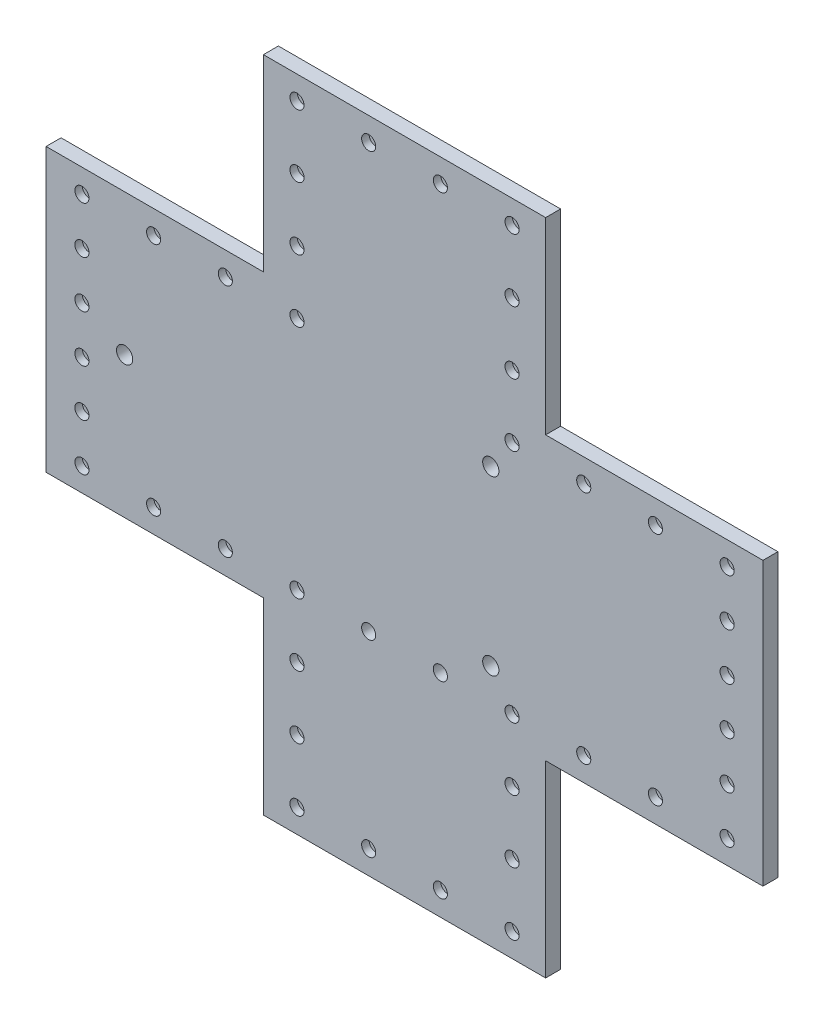
SolidWorks part; units mm, degrees
ref_plane "Front Plane" through (0, 0, 0) normal (0, 0, 1) x (1, 0, 0)
ref_plane "Top Plane" through (0, 0, 0) normal (0, 1, 0) x (1, 0, 0)
ref_plane "Right Plane" through (0, 0, 0) normal (1, 0, 0) x (0, 0, -1)
sketch "Sketch1" plane through (0, 0, 0) normal (0, 0, 1) x (1, 0, 0)
  line L1 (0, 0) -> (152.4, 0)
  line L2 (0, 0) -> (0, -60)
  line L3 (0, -60) -> (152.4, -60)
  line L4 (152.4, 0) -> (152.4, -60)
  line L6 (46.2, 0) -> (46.2, 40)
  line L7 (46.2, 40) -> (106.2, 40)
  line L8 (106.2, 40) -> (106.2, 0)
  line L9 (46.2, -60) -> (46.2, -100)
  line L10 (46.2, -100) -> (106.2, -100)
  line L11 (106.2, -100) -> (106.2, -60)
  line L12 (53.34, -55) -> (53.34, -68.3333) construction
  line L13 (53.34, -68.3333) -> (53.34, -81.6667) construction
  line L14 (53.34, -81.6667) -> (53.34, -95) construction
  line L15 (53.34, -95) -> (68.58, -95) construction
  line L16 (68.58, -95) -> (83.82, -95) construction
  line L17 (83.82, -95) -> (99.06, -95) construction
  line L18 (99.06, -95) -> (99.06, -81.6667) construction
  line L19 (99.06, -81.6667) -> (99.06, -68.3333) construction
  line L20 (99.06, -68.3333) -> (99.06, -55) construction
  line L21 (0, -30) -> (152.4, -30) construction
  circle A0 centre (7.62, -55) radius 1.5
  circle A1 centre (22.86, -55) radius 1.5
  circle A2 centre (38.1, -55) radius 1.5
  circle A3 centre (53.34, -55) radius 1.5
  circle A4 centre (68.58, -55) radius 1.5
  circle A5 centre (83.82, -55) radius 1.5
  circle A6 centre (99.06, -55) radius 1.5
  circle A7 centre (114.3, -55) radius 1.5
  circle A8 centre (129.54, -55) radius 1.5
  circle A9 centre (144.78, -55) radius 1.5
  circle A10 centre (53.34, -68.3333) radius 1.5
  circle A11 centre (53.34, -81.6667) radius 1.5
  circle A12 centre (53.34, -95) radius 1.5
  circle A13 centre (68.58, -95) radius 1.5
  circle A14 centre (83.82, -95) radius 1.5
  circle A15 centre (99.06, -95) radius 1.5
  circle A16 centre (99.06, -81.6667) radius 1.5
  circle A17 centre (99.06, -68.3333) radius 1.5
  circle A18 centre (7.62, -45) radius 1.5
  circle A19 centre (7.62, -35) radius 1.5
  circle A20 centre (144.78, -45) radius 1.5
  circle A21 centre (144.78, -35) radius 1.5
  circle A22 centre (144.78, -25) radius 1.5
  circle A23 centre (144.78, -15) radius 1.5
  circle A24 centre (144.78, -5) radius 1.5
  circle A25 centre (129.54, -5) radius 1.5
  circle A26 centre (114.3, -5) radius 1.5
  circle A27 centre (99.06, -5) radius 1.5
  circle A28 centre (99.06, 8.3333) radius 1.5
  circle A29 centre (99.06, 21.6667) radius 1.5
  circle A30 centre (99.06, 35) radius 1.5
  circle A31 centre (83.82, 35) radius 1.5
  circle A32 centre (68.58, 35) radius 1.5
  circle A33 centre (53.34, 35) radius 1.5
  circle A34 centre (53.34, 21.6667) radius 1.5
  circle A35 centre (53.34, 8.3333) radius 1.5
  circle A36 centre (53.34, -5) radius 1.5
  circle A37 centre (38.1, -5) radius 1.5
  circle A38 centre (22.86, -5) radius 1.5
  circle A39 centre (7.62, -5) radius 1.5
  circle A40 centre (7.62, -15) radius 1.5
  circle A41 centre (7.62, -25) radius 1.5
  point P20 (76.2, 40)
  point P21 (76.2, 0)
  dimension "D4" = 3
  dimension "D1" = 60
  dimension "D2" = 40
  dimension "D3" = 60
  dimension "D5" = 5
  dimension "D6" = 7.62
  dimension "D7" = 152.4
  dimension "D9" = 7.62
  dimension "D10" = 5
  dimension "D12" = 10
  dimension "D14" = 46.2
  dimension "D8" = 10
  dimension "D11" = 3
  dimension "D13" = 3
extrude "Boss-Extrude1" add sketch "Sketch1" along normal blind 3.18 contours L4 L1 L2 L3 A40 A38 A36 A26 A24 A22 A21 A20 A19 A18 A9 A8 A7 A6 A5 A4 A3 A2 A1 A0 A23 | L8 L7 L6 L1 A34 A32 A30 A28 A29 A31 A33 A35 | L10 L11 L3 L9 A17 A16 A15 A14 A13 A12 A11 A10 region at (76.2, -29.9606, 0) region at (76.2, 19.8793, 0) region at (76.2, -79.8793, 0)
extrude "Boss-Extrude2" add sketch "Sketch1<6>" along normal blind 1.59 contours A39 | A38 | A40 | A36 | A37 | A35 | A34 | A33 | A32 | A30 | A31 | A28 | A29 | A27 | A26 | A25 | A24 | A23 | A22 | A21 | A20 | A9 | A8 | A7 | A6 | A17 | A16 | A15 | A14 | A13 | A11 | A12 | A10 | A3 | A2 | A1 | A41 | A19 | A18 | A0 region at (7.62, -55, 0) region at (22.86, -55, 0) region at (38.1, -55, 0) region at (53.34, -55, 0) region at (99.06, -55, 0) region at (114.3, -55, 0) region at (129.54, -55, 0) region at (144.78, -55, 0) region at (53.34, -68.3333, 0) region at (53.34, -81.6667, 0) region at (53.34, -95, 0) region at (68.58, -95, 0) region at (83.82, -95, 0) region at (99.06, -95, 0) region at (99.06, -81.6667, 0) region at (99.06, -68.3333, 0) region at (7.62, -45, 0) region at (7.62, -35, 0) region at (144.78, -45, 0) region at (144.78, -35, 0) region at (144.78, -25, 0) region at (144.78, -15, 0) region at (144.78, -5, 0) region at (129.54, -5, 0) region at (114.3, -5, 0) region at (99.06, -5, 0) region at (99.06, 8.3333, 0) region at (99.06, 21.6667, 0) region at (99.06, 35, 0) region at (83.82, 35, 0) region at (68.58, 35, 0) region at (53.34, 35, 0) region at (53.34, 21.6667, 0) region at (53.34, 8.3333, 0) region at (53.34, -5, 0) region at (38.1, -5, 0) region at (22.86, -5, 0) region at (7.62, -5, 0) region at (7.62, -15, 0) region at (7.62, -25, 0)
sketch "Sketch1<6>" plane through (0, 0, 0) normal (0, 0, 1) x (1, 0, 0) same geometry as "Sketch1"
sketch "Sketch2" plane through (0, 0, 3.18) normal (0, 0, 1) x (1, 0, 0)
  line L0 (0, 0) -> (0, -60) construction
  line L1 (0, 46.2) -> (152.4, 46.2)
  line L2 (0, 46.2) -> (0, -106.2)
  line L3 (0, -106.2) -> (152.4, -106.2)
  line L4 (152.4, 46.2) -> (152.4, -106.2)
  circle A0 centre (12.7, 33.5) radius 6.342 construction
  circle A1 centre (94.5382, -11.6618) radius 1.725
  circle A2 centre (94.5382, -48.3382) radius 1.725
  circle A3 centre (16.7, -30) radius 1.725
  circle A4 centre (139.7, -30) radius 6.342 construction
  circle A5 centre (12.7, -93.5) radius 6.342 construction
  circle A8 centre (38.1, 33.5) radius 3.2639
  circle A9 centre (12.7, 8.1) radius 3.2639
  circle A10 centre (114.3, 33.5) radius 3.2639
  circle A11 centre (139.7, 8.1) radius 3.2639
  circle A12 centre (139.7, -68.1) radius 3.2639
  circle A13 centre (114.3, -93.5) radius 3.2639
  circle A14 centre (38.1, -93.5) radius 3.2639
  circle A15 centre (12.7, -68.1) radius 3.2639
  point P4 (0, 0)
  point P9 (0, 0)
  point P10 (0, 0)
  point P12 (0, 0)
  point P13 (0, 0)
  point P16 (0, 0)
  point P17 (-1.9641, -43.3163)
  point P18 (0, 0)
  point P21 (0, 0)
  point P23 (0, 0)
  point P26 (0, 0)
  point P27 (0, 0)
  point P28 (0, 0)
  point P29 (0, 0)
  point P32 (0, 0)
  point P35 (0, 0)
  point P38 (0, 0)
  point P41 (0, 0)
  point P44 (0, 0)
  point P47 (0, 0)
  point P50 (0, 0)
  point P53 (0, 0)
  point P54 (0, 0)
  point P55 (0, 0)
  point P56 (0, -104.7379)
  point P57 (0, 0)
  point P58 (-10.2274, 48.2066)
  point P61 (152.4, 25.034)
  point P62 (152.4, -72.1036)
  point P63 (0, -30)
  point P64 (139.7, 8.1)
  point P65 (12.7, 33.5)
  point P66 (38.1, 33.5)
  dimension "D1" = 3.45
  dimension "D22" = 12.684
  dimension "D23" = 6.5278
  dimension "D2" = 152.4
  dimension "D3" = 152.4
  dimension "D4" = 38.1
  dimension "D5" = 12.7
  dimension "D6" = 12.7
  dimension "D7" = 38.1
  dimension "D8" = 76.2
  dimension "D9" = 76.2
  dimension "D10" = 25.4
  dimension "D11" = 25.4
  dimension "D12" = 76.2
  dimension "D13" = 57.8618
  dimension "D14" = 57.8618
  dimension "D15" = 16.7
  dimension "D16" = 77.8382
  dimension "D17" = 12.7
  dimension "D18" = 12.7
  dimension "D19" = 76.2
  dimension "D20" = 12.7
  dimension "D21" = 12.7
extrude "Cut-Extrude1" cut sketch "Sketch2" against normal through all both contours A1 | A2 | A3 region at (94.5382, -11.6618, 3.18) region at (94.5382, -48.3382, 3.18) region at (16.7, -30, 3.18)
